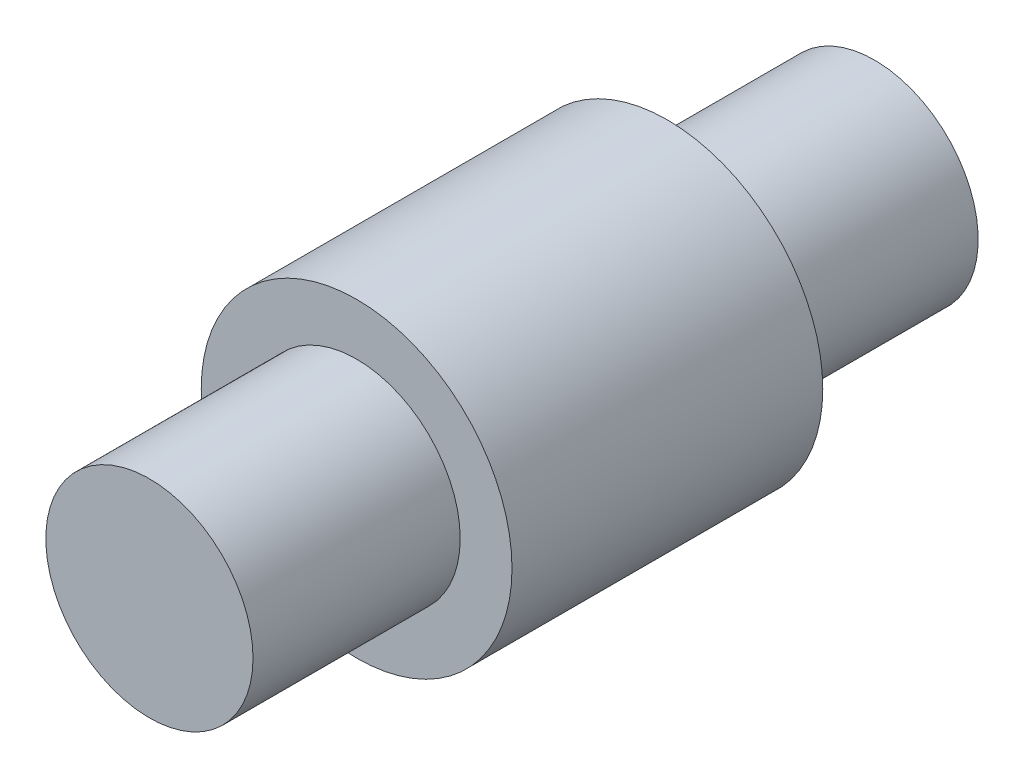
SolidWorks part; units mm, degrees
material "6061-T6 (SS)"
ref_plane "Front Plane" through (0, 0, 0) normal (0, 0, 1) x (1, 0, 0)
ref_plane "Top Plane" through (0, 0, 0) normal (0, 1, 0) x (1, 0, 0)
ref_plane "Right Plane" through (0, 0, 0) normal (1, 0, 0) x (0, 0, -1)
sketch "Sketch1" plane through (0, 0, 0) normal (0, 0, 1) x (1, 0, 0)
  circle A0 centre (0, 0) radius 15
  dimension "D1" = 30
extrude "Boss-Extrude1" add sketch "Sketch1" along normal mid plane 30
sketch "Sketch2" plane through (0, 0, 15) normal (0, 0, 1) x (1, 0, 0)
  circle A0 centre (0, 0) radius 10
  dimension "D1" = 20
extrude "Boss-Extrude2" add sketch "Sketch2" along normal blind 20
sketch "Sketch3" plane through (0, 0, -15) normal (0, 0, -1) x (-1, 0, 0)
  circle A0 centre (0, 0) radius 10
  dimension "D1" = 20
extrude "Boss-Extrude3" add sketch "Sketch3" along normal blind 20
ref_axis "Axis1" through (0, 0, -38.5) along (0, 0, 1)
